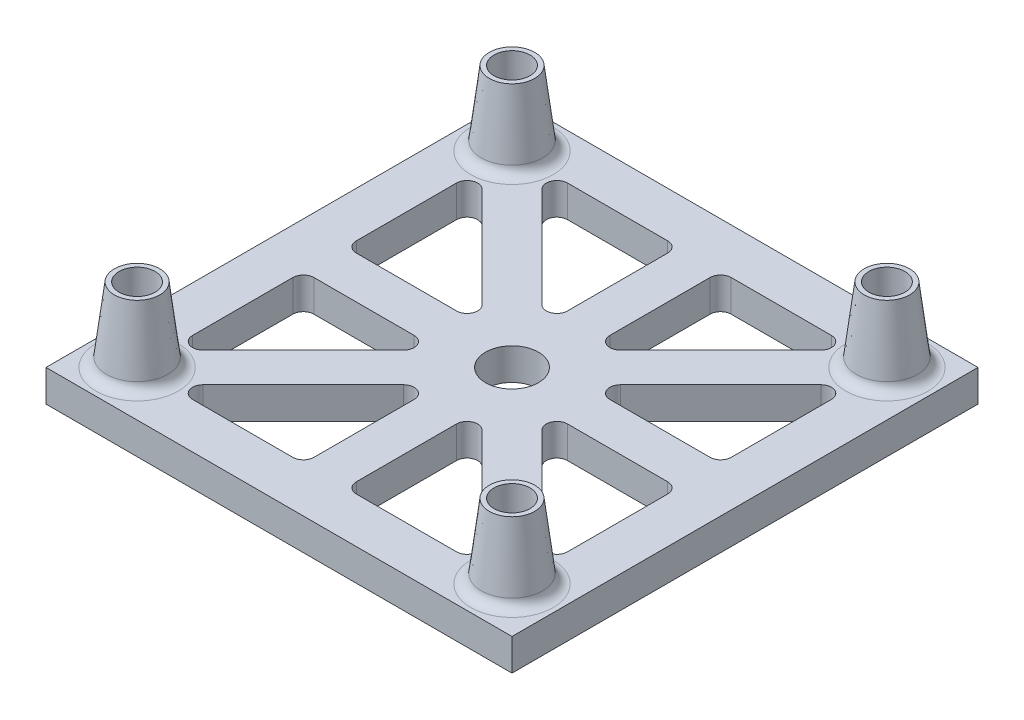
SolidWorks part; units mm, degrees
ref_plane "Front Plane" through (0, 0, 0) normal (0, 0, 1) x (1, 0, 0)
ref_plane "Top Plane" through (0, 0, 0) normal (0, 1, 0) x (1, 0, 0)
ref_plane "Right Plane" through (0, 0, 0) normal (1, 0, 0) x (0, 0, -1)
sketch "Sketch1" plane through (0, 0, 0) normal (0, 1, 0) x (1, 0, 0)
  line L0 (0, 0) -> (0, 22) construction
  line L1 (-22, 22) -> (22, 22)
  line L2 (-22, 22) -> (-22, -22)
  line L3 (-22, -22) -> (22, -22)
  line L4 (22, 22) -> (22, -22)
  line L5 (0, 0) -> (22, 0) construction
  dimension "D1" = 44
  dimension "D2" = 44
extrude "Boss-Extrude1" add sketch "Sketch1" along normal blind 3
sketch "Sketch2" plane through (0, 3, 0) normal (0, 1, 0) x (1, 0, 0)
  line L0 (0, 0) -> (0, 22) construction
  line L1 (22, 22) -> (-22, 22) construction
  line L2 (0, 0) -> (-22, 0) construction
  line L3 (-22, 22) -> (-22, -22) construction
  circle A0 centre (-17.7, 17.7) radius 3
  circle A1 centre (0, 0) radius 3.9285 construction
  dimension "D1" = 6
  dimension "D2" = 17.7
  dimension "D3" = 17.7
extrude "Boss-Extrude2" add sketch "Sketch2" along normal blind 7 draft 7
fillet "Fillet1" [suppressed] radius 1
ref_point "Point1"
ref_axis "Axis1" through (-17.7, 3, -17.7) along (0, 1, 0)
ref_plane "Plane1" through (-17.7, 0, 0) normal (-1, 0, 0) x (0, 1, 0)
sketch "Sketch3" plane through (-17.7, 0, 0) normal (-1, 0, 0) x (0, 1, 0)
  line L0 (0, 17.7) -> (0, 20.5)
  line L1 (0, 20.5) -> (1.8, 20.1826)
  line L2 (1.8, 20.1826) -> (3.8, 20.1826)
  line L3 (3.8, 20.1826) -> (3.8, 19.4)
  line L4 (3.8, 19.4) -> (10, 19.4)
  line L5 (10, 19.4) -> (10, 17.7)
  line L6 (10, 17.7) -> (0, 17.7)
  line L8 (3, 17.7) -> (4.9979, 17.7) construction
  dimension "D1" = 2.8
  dimension "D2" = 80
  dimension "D3" = 3.8
  dimension "D4" = 2
  dimension "D5" = 1.7
revolve "Cut-Revolve1" cut sketch "Sketch3" angle 360 about L6
sketch "Sketch4" plane through (0, 3, 0) normal (0, 1, 0) x (1, 0, 0)
  line L0 (-14.8716, 17.7) -> (-2, 17.7)
  line L1 (-2, 17.7) -> (-2, 4.8284)
  line L2 (-2, 4.8284) -> (-14.8716, 17.7)
  line L3 (-22, 22) -> (0, 0) construction
  line L4 (0, 0) -> (0, 22) construction
  line L5 (-17.7, 2) -> (-4.8284, 2)
  line L6 (-17.7, 14.8716) -> (-17.7, 2)
  line L7 (-4.8284, 2) -> (-17.7, 14.8716)
  circle A0 centre (0, 0) radius 2.5
  dimension "D1" = 5
  dimension "D2" = 2
  dimension "D3" = 2
extrude "Cut-Extrude1" cut sketch "Sketch4" against normal through all
fillet "Fillet2" radius 1 6 edges at (-2, 1.5, -4.8284) (-2, 1.5, -17.7) (-14.8716, 1.5, -17.7) (-17.7, 1.5, -2) (-17.7, 1.5, -14.8716) (-4.8284, 1.5, -2)
pattern_circular "CirPattern1" count 4 over 360 about axis through (0, 0, 0) along (0, 1, 0) of "Boss-Extrude2", "Cut-Revolve1", "Cut-Extrude1", "Fillet2"
fillet "Fillet3" radius 1 4 edges at (-17.7, 3, -14.7) (-14.7, 3, 17.7) (17.7, 3, 14.7) (14.7, 3, -17.7)
